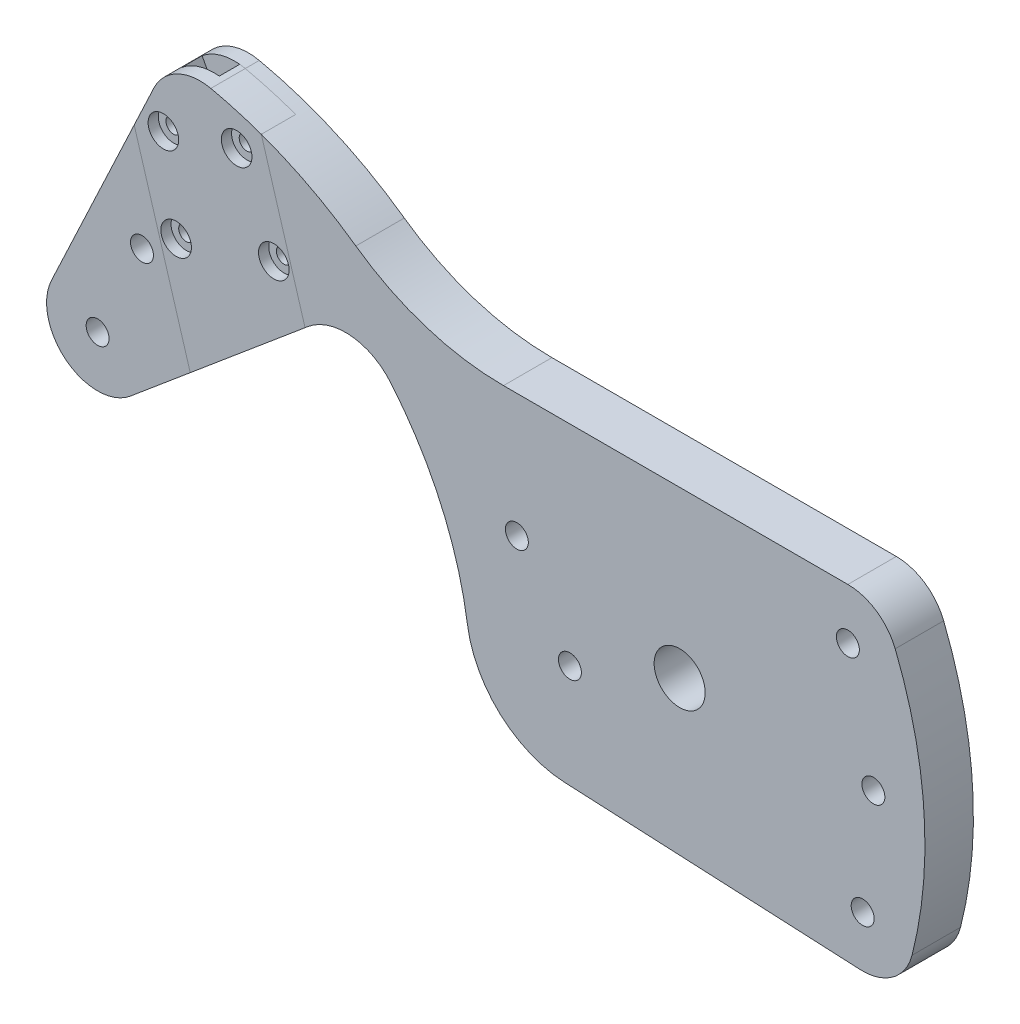
SolidWorks part; units mm, degrees
ref_plane "Front Plane" through (0, 0, 0) normal (0, 0, 1) x (1, 0, 0)
ref_plane "Top Plane" through (0, 0, 0) normal (0, 1, 0) x (1, 0, 0)
ref_plane "Right Plane" through (0, 0, 0) normal (1, 0, 0) x (0, 0, -1)
sketch "Sketch1" plane through (0, 0, 0) normal (0, 0, 1) x (1, 0, 0)
  line L1 (-5, -5) -> (5, -5) construction
  line L2 (-5, -5) -> (-5, 5) construction
  line L3 (-5, 5) -> (5, 5) construction
  line L4 (5, -5) -> (5, 5) construction
  line L5 (-5, -5) -> (5, 5) construction
  line L6 (-5, 5) -> (5, -5) construction
  line L7 (35.3984, -31.7883) -> (-22.5002, -28.984)
  line L9 (-114.4671, 24.4556) -> (-123.1671, 5.9556)
  line L10 (-107.6899, -5.9604) -> (-72.8648, 23.2613)
  line L11 (-114.4671, 24.4556) -> (-103.0859, 48.6569)
  line L16 (-65.4725, 14.4515) -> (-108.3178, -21.5) construction
  line L17 (50.9822, -33.5) -> (-177.2181, -33.5) construction
  line L20 (-34.5382, 32.4) -> (32.9822, 32.4)
  circle A0 centre (0, 0) radius 5
  circle A1 centre (-31.9178, 8.2) radius 2.25
  circle A2 centre (-21.5178, -8.7) radius 2.25
  circle A3 centre (32.9822, 22.4) radius 2.25
  circle A4 centre (37.9822, -0.1) radius 2.25
  circle A5 centre (35.8822, -21.8) radius 2.25
  circle A6 centre (35.8822, -21.8) radius 2.25 construction
  circle A7 centre (37.9822, -0.1) radius 2.25 construction
  circle A8 centre (32.9822, 22.4) radius 2.25 construction
  circle A9 centre (-31.9178, 8.2) radius 2.25 construction
  circle A10 centre (-21.5178, -8.7) radius 2.25 construction
  arc A12 (-41.6083, -11.6627) -> (-22.5002, -28.984) centre (-21.5178, -8.7) ccw
  arc A13 (32.5913, -31.6523) -> (28.0429, 32.4) centre (-33.3577, -4.1478) ccw construction
  arc A14 (45.5723, -24.2704) -> (42.2664, 26.1153) centre (-33.3577, -4.1478) ccw
  arc A15 (35.3984, -31.7883) -> (45.5723, -24.2704) centre (35.8822, -21.8) ccw
  arc A16 (42.2664, 26.1153) -> (32.9822, 32.4) centre (32.9822, 22.4) ccw
  circle A17 centre (-105.4178, 20.2) radius 2.25
  circle A18 centre (-33.3577, -4.1478) radius 81.4546 construction
  circle A19 centre (-114.1178, 1.7) radius 2.25
  circle A21 centre (-105.4178, 20.2) radius 2.25 construction
  circle A22 centre (-114.1178, 1.7) radius 2.25 construction
  circle A23 centre (-105.4178, 20.2) radius 10 construction
  arc A24 (-123.1671, 5.9556) -> (-107.6899, -5.9604) centre (-114.1178, 1.7) ccw
  arc A27 (-91.9187, 54.1744) -> (-103.0859, 48.6569) centre (-94.0366, 44.4013) ccw
  circle A31 centre (-33.3577, -4.1478) radius 71.4546 construction
  arc A32 (-41.6083, -11.6627) -> (-56.6627, 21.8438) centre (-108.3178, -21.5) ccw
  arc A33 (-31.0568, -26.628) -> (-91.9187, 54.1744) centre (-108.3178, -21.5) ccw
  arc A34 (-63.487, 41.6328) -> (-34.5382, 32.4) centre (-34.5382, 82.4) ccw
  arc A35 (-56.6627, 21.8438) -> (-72.8648, 23.2613) centre (-65.4725, 14.4515) ccw
  circle A36 centre (-65.4725, 14.4515) radius 10.5004 construction
  circle A37 centre (-108.3178, -21.5) radius 67.4309 construction
  circle A38 centre (-108.3178, -21.5) radius 77.4309 construction
  circle A39 centre (-108.3178, -21.5) radius 10.5004 construction
  circle A40 centre (-108.3178, -21.5) radius 11.5004 construction
  circle A41 centre (0, 0) radius 33 construction
  point P35 (50.3427, -4.5217)
  point P37 (37.1696, 16.7103)
  point P54 (-36.0565, -0.0269)
  point P75 (-40.8381, -1.4887)
  dimension "D1" = 10
  dimension "D3" = 10
  dimension "D5" = 50
  dimension "D7" = 40
  dimension "D4" = 10
  dimension "D2" = 10
  dimension "D8" = 1
extrude "Boss-Extrude1" add sketch "Sketch1" along normal mid plane 9.5 contours A0 L4 L3 | A0 L1 L4 | A0 L2 L1 | A0 L3 L2 | A35 A32 A12 A33 A27 L11 L9 A24 L10 A17 A19 region at (6.5137, -29.0519, 0) region at (-82.595, 21.4109, 0)
sketch "Sketch2" plane through (0, 0, 0) normal (0, 0, 1) x (1, 0, 0)
  line L0 (-94.0366, 44.4013) -> (-96.9145, 53.9782) construction
  line L1 (-78.2271, 18.7618) -> (-72.8648, 23.2613)
  line L2 (-94.0366, 44.4013) -> (-84.6999, 13.3304) construction
  line L3 (-92.0846, 44.9879) -> (-78.2271, 18.7618)
  line L4 (-95.0124, 54.3536) -> (-94.0366, 44.4013) construction
  line L5 (-94.0366, 44.4013) -> (-90.5122, 8.4534) construction
  line L6 (-98.7084, 53.2429) -> (-94.0366, 44.4013) construction
  line L7 (-94.0366, 44.4013) -> (-79.7943, 17.4467) construction
  line L8 (-100.3823, 52.1299) -> (-95.9887, 43.8147)
  line L9 (-93.0022, 54.3476) -> (-92.0846, 44.9879)
  line L12 (-92.369, 6.8953) -> (-78.2271, 18.7618)
  line L13 (-107.6899, -5.9604) -> (-72.8648, 23.2613) construction
  line L14 (-101.3327, 53.9285) -> (-91.0539, 34.4751) construction
  line L15 (-93.2007, 56.3721) -> (-91.0539, 34.4751) construction
  line L16 (-95.9887, 43.8147) -> (-92.369, 6.8953)
  line L18 (-97.0194, 54.3274) -> (-78.2271, 18.7618) construction
  line L19 (-97.0194, 54.3274) -> (-92.369, 6.8953) construction
  line L20 (-92.369, 6.8953) -> (-107.6899, -5.9604)
  line L22 (-94.0366, 44.4013) -> (-90.3786, 7.0905) construction
  line L23 (-94.0366, 44.4013) -> (-79.9955, 17.8274) construction
  arc A0 (-93.0022, 54.3476) -> (-100.3823, 52.1299) centre (-94.0366, 44.4013) ccw
  arc A1 (-95.0124, 54.3536) -> (-98.7084, 53.2429) centre (-94.0366, 44.4013) ccw construction
  arc A2 (-93.2007, 56.3721) -> (-101.3327, 53.9285) centre (-94.0366, 44.4013) ccw construction
  arc A3 (-91.9187, 54.1744) -> (-103.0859, 48.6569) centre (-94.0366, 44.4013) ccw construction
  point P33 (-96.9145, 53.9782)
  dimension "D3" = 7
  dimension "D4" = 20
  dimension "D1" = 2
  dimension "D2" = 2
extrude "Cut-Extrude1" cut sketch "Sketch2" against normal mid plane 4 contours A0 L8 L12 L9 region at (-89.8285, 28.8905, 0)
ref_plane "Plane1" through (-20.0256, 66.6414, 0) normal (-0.2878, 0.9577, 0) x (0.9577, 0.2878, 0)
sketch "Sketch4" plane through (0, 0, 4.75) normal (0, 0, 1) x (1, 0, 0)
  line L10 (-101.2193, 42.2429) -> (-86.8539, 46.5597) construction
  line L11 (-17.9186, 67.2745) -> (-22.1325, 66.0083) construction
  line L12 (-98.7212, 25.2426) -> (-79.5673, 30.9983) construction
  line L13 (-94.0366, 44.4013) -> (-89.1443, 28.1205) construction
  line L15 (-92.0846, 44.9879) -> (-93.0022, 54.3476)
  line L16 (-78.2271, 18.7618) -> (-92.0846, 44.9879)
  line L17 (-92.369, 6.8953) -> (-78.2271, 18.7618)
  line L18 (-95.9887, 43.8147) -> (-92.369, 6.8953)
  line L19 (-100.3823, 52.1299) -> (-95.9887, 43.8147)
  line L20 (-92.0846, 44.9879) -> (-93.0022, 54.3476) construction
  line L21 (-78.2271, 18.7618) -> (-92.0846, 44.9879) construction
  line L22 (-92.369, 6.8953) -> (-78.2271, 18.7618) construction
  line L23 (-95.9887, 43.8147) -> (-92.369, 6.8953) construction
  line L24 (-100.3823, 52.1299) -> (-95.9887, 43.8147) construction
  circle A0 centre (-98.7212, 25.2426) radius 1.5
  circle A1 centre (-101.2193, 42.2429) radius 1.5
  circle A2 centre (-86.8539, 46.5597) radius 1.5
  circle A3 centre (-79.5673, 30.9983) radius 1.5
  arc A7 (-93.0022, 54.3476) -> (-100.3823, 52.1299) centre (-94.0366, 44.4013) ccw
  arc A8 (-93.0022, 54.3476) -> (-100.3823, 52.1299) centre (-94.0366, 44.4013) ccw construction
  point P13 (-94.0366, 44.4013)
  dimension "D3" = 3
  dimension "D2" = 17
  dimension "D4" = 15
  dimension "D5" = 20
  dimension "D1" = 0
extrude "Cut-Extrude2" cut sketch "Sketch4" against normal through all
sketch "Sketch5" plane through (0, 0, 4.75) normal (0, 0, 1) x (1, 0, 0)
  circle A49 centre (-101.2193, 42.2429) radius 3
  circle A50 centre (-86.8539, 46.5597) radius 3
  circle A51 centre (-79.5673, 30.9983) radius 3
  circle A52 centre (-98.7212, 25.2426) radius 3
  dimension "D1" = 6
extrude "Cut-Extrude3" cut sketch "Sketch5" against normal blind 2
sketch "Sketch3" plane through (-20.0256, 66.6414, 0) normal (-0.2878, 0.9577, 0) x (0.9577, 0.2878, 0)
  line L0 (-90.7804, 2) -> (-63.7804, 2)
  line L1 (-63.7804, 2) -> (-63.7804, -4.75)
  line L2 (-72.4396, -4.75) -> (-48.8199, -4.75) construction
  line L3 (-90.7804, 2) -> (-90.7804, -4.75)
  line L4 (-116.2426, -4.75) -> (-84.7222, -4.75) construction
  line L11 (-79.3187, 2) -> (-75.2421, 2) construction
  point P3 (-77.2804, 2)
  point P11 (-77.2804, 2)
  point P12 (-98.2368, 0)
  dimension "D1" = 27
split "Split3" trim tools "Sketch3" bodies to split 111 resulting bodies 112 113
